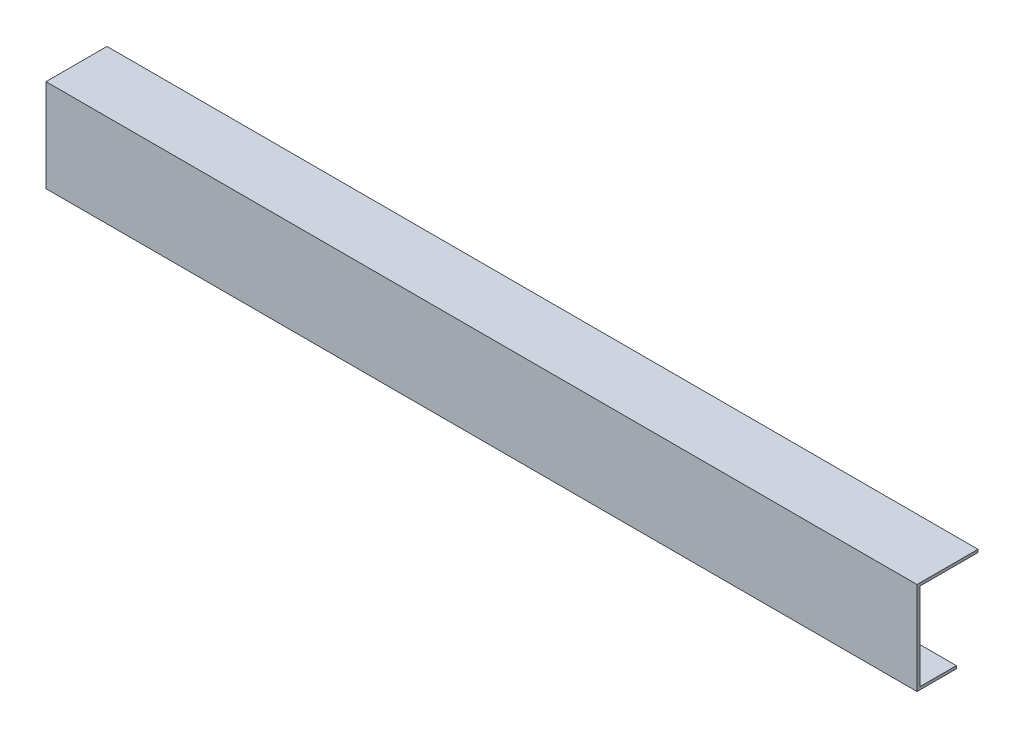
SolidWorks part; units mm, degrees
ref_plane "Front Plane" through (0, 0, 0) normal (0, 0, 1) x (1, 0, 0)
ref_plane "Top Plane" through (0, 0, 0) normal (0, 1, 0) x (1, 0, 0)
ref_plane "Right Plane" through (0, 0, 0) normal (1, 0, 0) x (0, 0, -1)
sketch "Sketch1" plane through (0, 0, 0) normal (0, 0, 1) x (1, 0, 0)
  line L1 (0, 0) -> (787.4, 0)
  line L2 (0, 0) -> (0, -83.82)
  line L3 (0, -83.82) -> (787.4, -83.82)
  line L4 (787.4, 0) -> (787.4, -83.82)
  dimension "D1" = 83.82
  dimension "D2" = 787.4
extrude "Boss-Extrude1" add sketch "Sketch1" along normal blind 55.118
sketch "Sketch2" plane through (787.4, 0, 0) normal (1, 0, 0) x (0, 0, -1)
  line L0 (-19.558, -83.82) -> (-19.558, -81.28)
  line L1 (-55.118, -83.82) -> (0, -83.82) construction
  line L2 (-19.558, -81.28) -> (-52.578, -81.28)
  line L3 (-52.578, -81.28) -> (-52.578, -2.54)
  line L4 (-52.578, -2.54) -> (0, -2.54)
  line L5 (0, -83.82) -> (0, 0) construction
  line L6 (0, -2.54) -> (0, -83.82)
  line L7 (0, -83.82) -> (-19.558, -83.82)
  line L8 (-55.118, -83.82) -> (-55.118, 0) construction
  line L9 (-55.118, 0) -> (0, 0) construction
  dimension "D1" = 35.56
  dimension "D2" = 2.54
  dimension "D3" = 2.54
  dimension "D4" = 2.54
extrude "Cut-Extrude1" cut sketch "Sketch2" against normal through all
